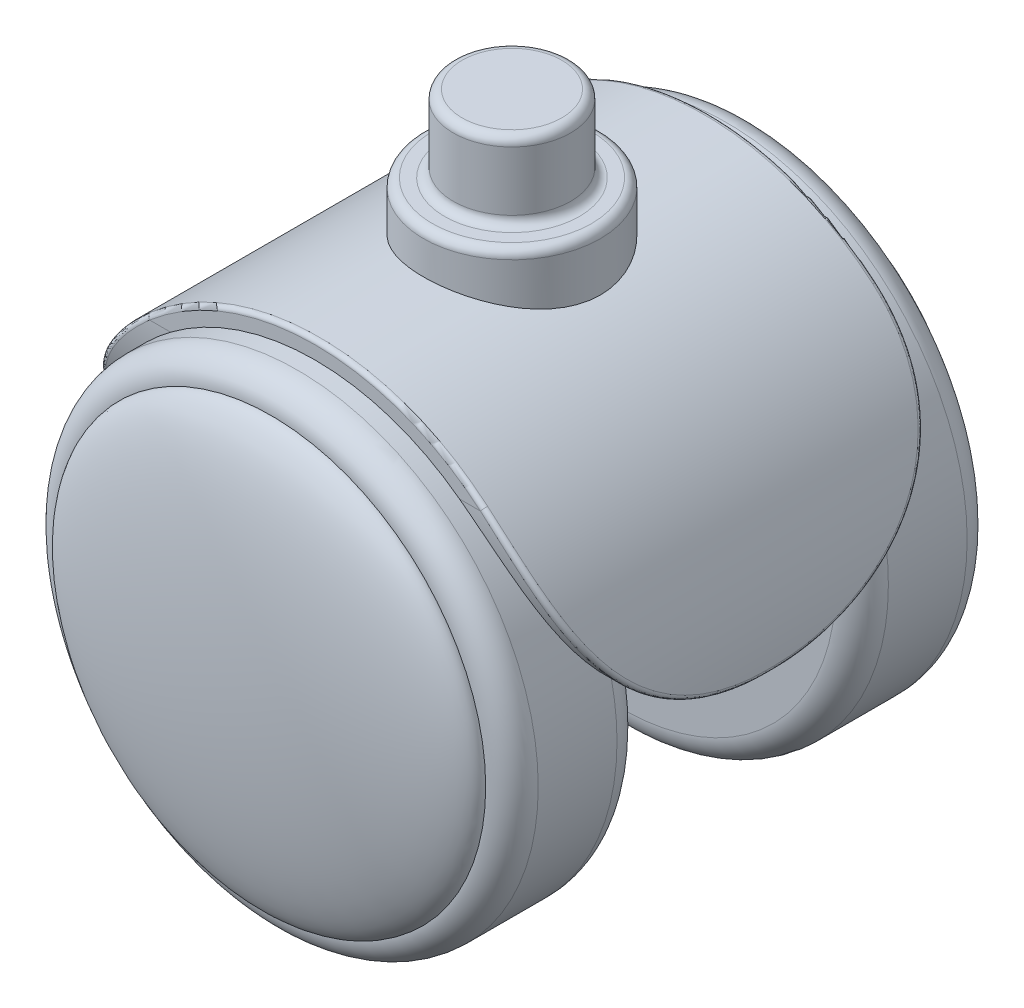
SolidWorks part; units mm, degrees
ref_plane "Front Plane" through (0, 0, 0) normal (0, 0, 1) x (1, 0, 0)
ref_plane "Top Plane" through (0, 0, 0) normal (0, 1, 0) x (1, 0, 0)
ref_plane "Right Plane" through (0, 0, 0) normal (1, 0, 0) x (0, 0, -1)
sketch "Sketch1" plane through (0, 0, 0) normal (0, 0, 1) x (1, 0, 0)
  circle A0 centre (0, 0) radius 27.5
  dimension "D1" = 55
extrude "Boss-Extrude1" add sketch "Sketch1" along normal blind 15
fillet "Fillet1" radius 3 2 edges at (27.5, 0, 0) (27.5, 0, 15)
dome "Dome1" faces to dome 1 distance 5 reverse direction no elliptical dome yes face at (24.5, 0, 15) parameters "D1"=5
ref_plane "Plane1" through (0, 0, -12.5) normal (0, 0, 1) x (1, 0, 0)
mirror "Mirror2" about plane through (0, 0, -12.5) normal (0, 0, 1) of bodies 101
sketch "Sketch4" plane through (0, 0, -12.5) normal (0, 0, 1) x (1, 0, 0)
  line L0 (-29.5, 0) -> (-27.5, 0)
  line L1 (27.5, 0) -> (29.5, 0)
  circle A0 centre (0, 0) radius 27.5 construction
  arc A1 (27.5, 0) -> (-27.5, 0) centre (0, 0) ccw
  arc A2 (29.5, 0) -> (-29.5, 0) centre (0, 0) ccw
  dimension "D1" = 2
extrude "Boss-Extrude2" add sketch "Sketch4" along normal mid plane 45 separate body
fillet "Fillet2" radius 22 4 edges at (28.5, 0, 10) (28.5, 0, -35) (-28.5, 0, 10) (-28.5, 0, -35)
fillet "Fillet3" radius 0.5 8 edges at (-27.7587, 9.9852, 6.4294) (-29.5, 0, -12.5) (-28.9573, 5.6326, -27.7006) (0, 29.5, -35) (27.7587, 9.9852, -31.4294) (29.5, 0, -12.5) (28.9573, 5.6326, 2.7006) (0, 29.5, 10)
sketch "Sketch5" plane through (0, 0, -12.5) normal (0, 0, 1) x (1, 0, 0)
  line L0 (0, 0) -> (0, 45.4894) construction
  line L1 (6.7013, -8.1964) -> (6.7013, 20.5004)
  line L2 (0, 0) -> (0, -9.1964)
  line L3 (0, -9.1964) -> (5.7013, -9.1964)
  line L8 (9.0989, 34.2897) -> (7.7013, 34.2897)
  line L9 (6.7013, 35.2897) -> (6.7013, 42.0482)
  line L10 (5.7013, 43.0482) -> (0, 43.0482)
  line L11 (0, 43.0482) -> (0, 0)
  line L12 (7.7013, 21.5004) -> (9.0989, 21.5004)
  line L13 (10.0989, 22.5004) -> (10.0989, 33.2897)
  arc A0 (6.7013, 42.0482) -> (5.7013, 43.0482) centre (5.7013, 42.0482) ccw
  arc A1 (7.7013, 34.2897) -> (6.7013, 35.2897) centre (7.7013, 35.2897) cw
  arc A2 (10.0989, 33.2897) -> (9.0989, 34.2897) centre (9.0989, 33.2897) ccw
  arc A3 (9.0989, 21.5004) -> (10.0989, 22.5004) centre (9.0989, 22.5004) ccw
  arc A4 (6.7013, 20.5004) -> (7.7013, 21.5004) centre (7.7013, 20.5004) cw
  arc A5 (6.7013, -8.1964) -> (5.7013, -9.1964) centre (5.7013, -8.1964) cw
  point P12 (6.7013, 34.2897)
  dimension "D1" = 1
revolve "Cut-Revolve1" cut sketch "Sketch5" angle 360 about L0
revolve "Revolve2" add sketch "Sketch5<2>" angle 360 about L0
sketch "Sketch5<2>" plane through (0, 0, -12.5) normal (0, 0, 1) x (1, 0, 0) same geometry as "Sketch5"
sketch "Sketch6" plane through (0, 0, -12.5) normal (0, 0, 1) x (1, 0, 0)
  circle A0 centre (0, 0) radius 4.7813
extrude "Cut-Extrude1" cut sketch "Sketch6" against normal mid plane 15
extrude "Boss-Extrude3" add sketch "Sketch6<2>" along normal mid plane 25
sketch "Sketch6<2>" plane through (0, 0, -12.5) normal (0, 0, 1) x (1, 0, 0) same geometry as "Sketch6"
